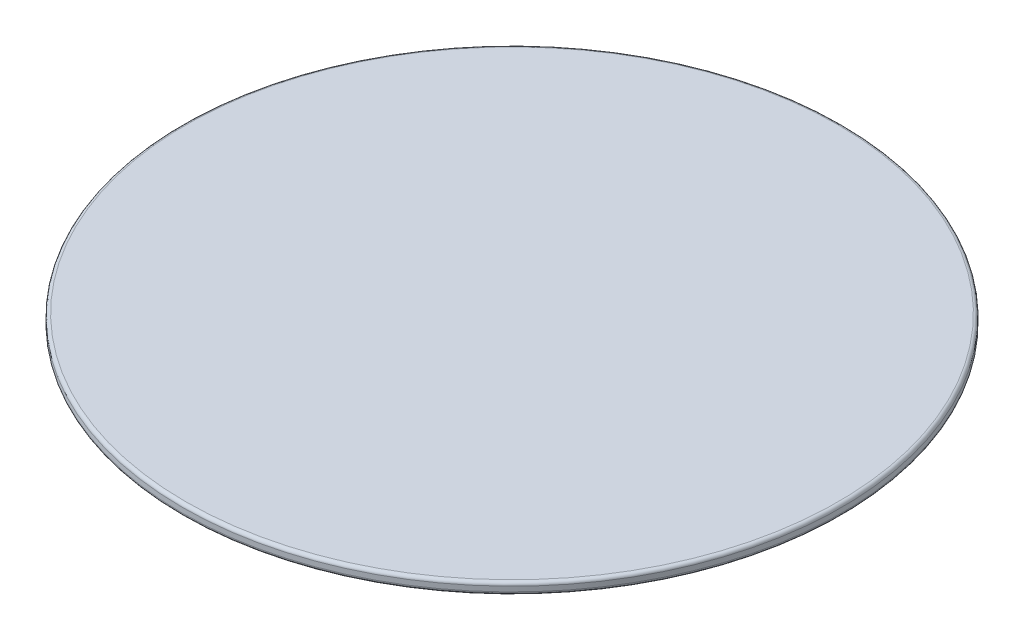
SolidWorks part; units mm, degrees
ref_plane "Front Plane" through (0, 0, 0) normal (0, 0, 1) x (1, 0, 0)
ref_plane "Top Plane" through (0, 0, 0) normal (0, 1, 0) x (1, 0, 0)
ref_plane "Right Plane" through (0, 0, 0) normal (1, 0, 0) x (0, 0, -1)
sketch "Sketch1" plane through (0, 0, 0) normal (0, 1, 0) x (1, 0, 0)
  circle A0 centre (0, 0) radius 100
  dimension "D1" = 200
extrude "Boss-Extrude1" add sketch "Sketch1" along normal blind 10
chamfer "Chamfer3" distance 12 angle 30 1 edges at (0, 0, 100)
sketch "Sketch7" plane through (0, 0, 0) normal (0, -1, 0) x (-1, 0, 0)
  circle A0 centre (0, 0) radius 35
  dimension "D1" = 70
extrude "Boss-Extrude5" add sketch "Sketch7" along normal blind 10
fillet "Fillet2" radius 1 2 edges at (0, 6.9282, 100) (0, 10, 100)
sketch "Sketch2" plane through (0, -10, 0) normal (0, -1, 0) x (1, 0, 0)
  circle A0 centre (0, 0) radius 30.5
  circle A1 centre (0, 0) radius 19.5
  dimension "D1" = 61
  dimension "D2" = 39
extrude "Cut-Extrude1" cut sketch "Sketch2" against normal blind 1
sketch "Sketch3" plane through (0, -10, 0) normal (0, -1, 0) x (-1, 0, 0)
  line L1 (1, -31.01) -> (-1, -31.01)
  line L2 (1, -31.01) -> (1, -29.99)
  line L3 (1, -29.99) -> (-1, -29.99)
  line L4 (-1, -31.01) -> (-1, -29.99)
  line L5 (1, -31.01) -> (-1, -29.99) construction
  line L6 (1, -29.99) -> (-1, -31.01) construction
  line L7 (1, -20.01) -> (-1, -20.01)
  line L8 (1, -20.01) -> (1, -18.99)
  line L9 (1, -18.99) -> (-1, -18.99)
  line L10 (-1, -20.01) -> (-1, -18.99)
  line L11 (1, -20.01) -> (-1, -18.99) construction
  line L12 (1, -18.99) -> (-1, -20.01) construction
  circle A0 centre (0, 0) radius 30.5 construction
  circle A1 centre (0, 0) radius 30.5 construction
  circle A2 centre (0, 0) radius 19.5 construction
  point P0 (0, -30.5)
  point P9 (0, -19.5)
  dimension "D1" = 2
  dimension "D2" = 1.02
  dimension "D3" = 1.02
  dimension "D4" = 2
extrude "Boss-Extrude2" add sketch "Sketch3" against normal blind 1
fillet "Fillet1" radius 1 4 edges at (-1, -9.5, 20.01) (1, -9.5, 20.01) (-1, -9.5, 29.99) (1, -9.5, 29.99)
pattern_circular "CirPattern1" count 8 over 360 about axis through (0, 0, 0) along (0, 1, 0) of "Boss-Extrude2", "Fillet1"
sketch "Sketch4" plane through (0, -10, 0) normal (0, -1, 0) x (1, 0, 0)
  circle A0 centre (0, 0) radius 8
  dimension "D1" = 16
extrude "Boss-Extrude3" add sketch "Sketch4" along normal blind 7
sketch "Sketch8" plane through (0, -17, 0) normal (0, -1, 0) x (1, 0, 0)
  circle A0 centre (0, 0) radius 4.5
  dimension "D1" = 9
extrude "Cut-Extrude3" cut sketch "Sketch8" against normal blind 22
chamfer "Chamfer2" distance 2 angle 45 1 edges at (0, -17, -4.5)
sketch "Sketch5" plane through (0, -17, 0) normal (0, -1, 0) x (-1, 0, 0)
  line L1 (-1.6, -5.4) -> (1.6, -5.4)
  line L2 (-1.6, -5.4) -> (-1.6, -3.8381)
  line L3 (-1.6, -3.8381) -> (1.6, -3.8381)
  line L4 (1.6, -5.4) -> (1.6, -3.8381)
  point P0 (0, -3.8381)
  dimension "D1" = 3.2
  dimension "D2" = 5.4
extrude "Cut-Extrude2" cut sketch "Sketch5" against normal up to surface (22 mm away) up to face at (0, 5, -4.5)
sketch "Sketch6" plane through (0, 5, 0) normal (0, -1, 0) x (-1, 0, 0)
  line L1 (0.85, 5.8799) -> (-0.85, 5.8799)
  line L2 (0.85, 5.8799) -> (0.85, 4)
  line L3 (0.85, 4) -> (-0.85, 4)
  line L4 (-0.85, 5.8799) -> (-0.85, 4)
  point P4 (0, 4)
  dimension "D1" = 1.7
  dimension "D2" = 4
extrude "Boss-Extrude4" add sketch "Sketch6" along normal up to vertex (20 mm away)
chamfer "Chamfer4" distance 2 distance2 0.4 1 edges at (0, -15, -4)
fillet "Fillet3" radius 1 2 edges at (-0.85, -4, -4) (0.85, -4, -4)
pattern_circular "CirPattern2" count 5 over 360 about axis through (0, 0, 0) along (0, 1, 0) of "Boss-Extrude4", "Chamfer4", "Fillet3"
sketch "Sketch9" plane through (0, 0, 0) normal (0, -1, 0) x (-1, 0, 0)
  circle A0 centre (0, 0) radius 37
  circle A1 centre (0, 0) radius 35
  dimension "D1" = 74
  dimension "D2" = 70
extrude "Boss-Extrude6" add sketch "Sketch9" along normal blind 22
sketch "Sketch10" plane through (0, -10, 0) normal (0, -1, 0) x (-1, 0, 0)
  circle A0 centre (0, 0) radius 35.5
  circle A1 centre (0, 0) radius 35
  dimension "D1" = 71
  dimension "D2" = 70
extrude "Cut-Extrude4" cut sketch "Sketch10" along normal through all
chamfer "Chamfer5" distance 0.5 angle 68 1 edges at (0, -22, -35.5)
